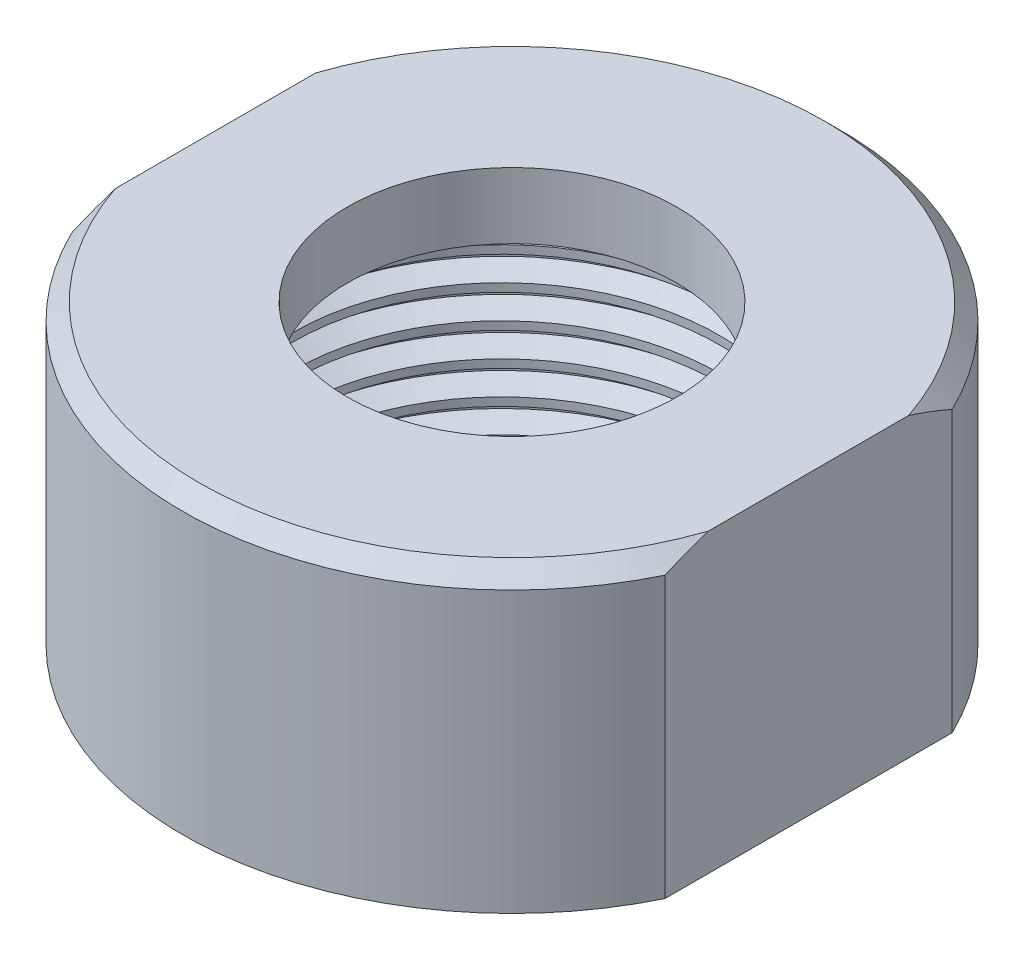
SolidWorks part; units mm, degrees
ref_plane "Front Plane" through (0, 0, 0) normal (0, 0, 1) x (1, 0, 0)
ref_plane "Top Plane" through (0, 0, 0) normal (0, 1, 0) x (1, 0, 0)
ref_plane "Right Plane" through (0, 0, 0) normal (1, 0, 0) x (0, 0, -1)
sketch "Sketch1" plane through (0, 0, 0) normal (0, 1, 0) x (1, 0, 0)
  circle A0 centre (0, 0) radius 10
  circle A1 centre (0, 0) radius 7
  dimension "D1" = 20
  dimension "D2" = 14
extrude "Boss-Extrude1" add sketch "Sketch1" along normal blind 7
sketch "Sketch3" plane through (0, 7, 0) normal (0, 1, 0) x (1, 0, 0)
  circle A0 centre (0, 0) radius 10
  circle A1 centre (0, 0) radius 5
  circle A2 centre (0, 0) radius 10 construction
  dimension "D1" = 10
extrude "Boss-Extrude2" add sketch "Sketch3" along normal blind 2
chamfer "Chamfer1" distance 0.5 angle 45 1 edges at (0, 9, 10)
thread "Thread1" pitch 1 method extrude profile "Thread Profile1" start angle 0, offset 0, length 0, pitch 1, diameter 14
ref_plane "Plane1" through (7, 0, 0) normal (0, 0, 1) x (1, 0, 0)
sketch "Thread Profile1" plane through (7, 0, 0) normal (0, 0, 1) x (1, 0, 0)
  line L0 (0, 0) -> (0, 1) construction
  line L11 (0, 0) -> (0, 0.875)
  line L12 (0, 0.875) -> (-0.5413, 0.5625)
  line L13 (-0.5413, 0.5625) -> (-0.5413, 0.3125)
  line L15 (-0.5413, 0.3125) -> (0, 0)
  line L17 (-0.5413, 0.4375) -> (0, 0.4375) construction
  point P2 (0, 0)
  dimension "Pitch" = 1
  dimension "Profile_Angle" = 60
  dimension "Profile_Land" = 0.25
  dimension "Profile_Height" = 0.5413
sketch "Sketch8" plane through (0, 9, 0) normal (0, 1, 0) x (1, 0, 0)
  line L1 (-9, 11.1099) -> (9, 11.1099)
  line L2 (-9, 11.1099) -> (-9, -11.1594)
  line L3 (-9, -11.1594) -> (9, -11.1594)
  line L4 (9, 11.1099) -> (9, -11.1594)
  dimension "D1" = 18
  dimension "D2" = 9
extrude "Cut-Extrude2" cut sketch "Sketch8" against normal blind 10 flip side to cut
equation "\"D2@Sketch8\"=\"D1@Sketch8\"/2"
